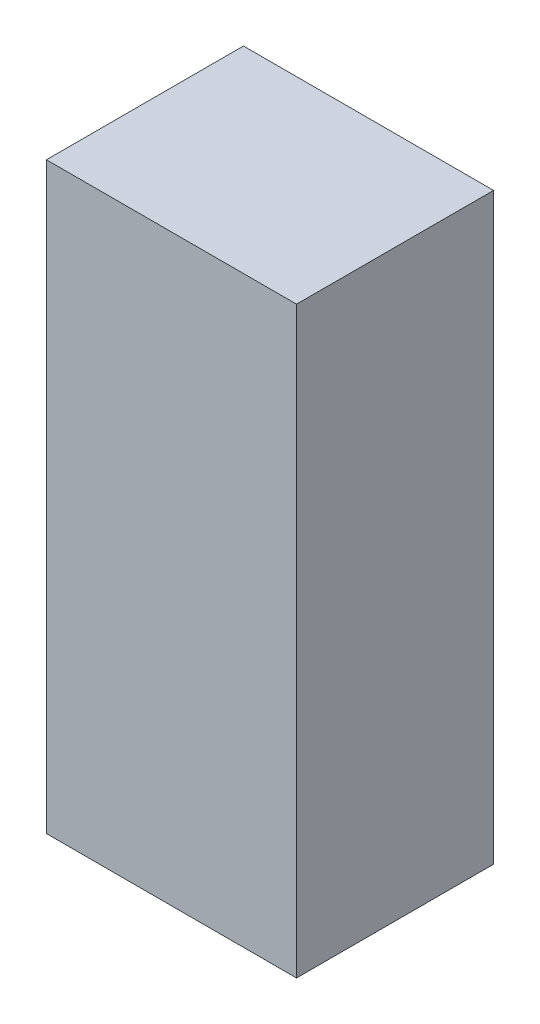
SolidWorks part; units mm, degrees
ref_plane "Front Plane" through (0, 0, 0) normal (1, 0, 0) x (0, 1, 0)
ref_plane "Top Plane" through (0, 0, 0) normal (0, 0, 1) x (0, 1, 0)
ref_plane "Right Plane" through (0, 0, 0) normal (0, 1, 0) x (-1, 0, 0)
sketch "Sketch1" plane through (0, 0, 0) normal (0, 0, 1) x (0, 1, 0)
  line L1 (0, 0) -> (77, 0)
  line L2 (0, 0) -> (0, 33)
  line L3 (0, 33) -> (77, 33)
  line L4 (77, 0) -> (77, 33)
  dimension "D1" = 77
  dimension "D2" = 33
extrude "Boss-Extrude1" add sketch "Sketch1" along normal blind 26
